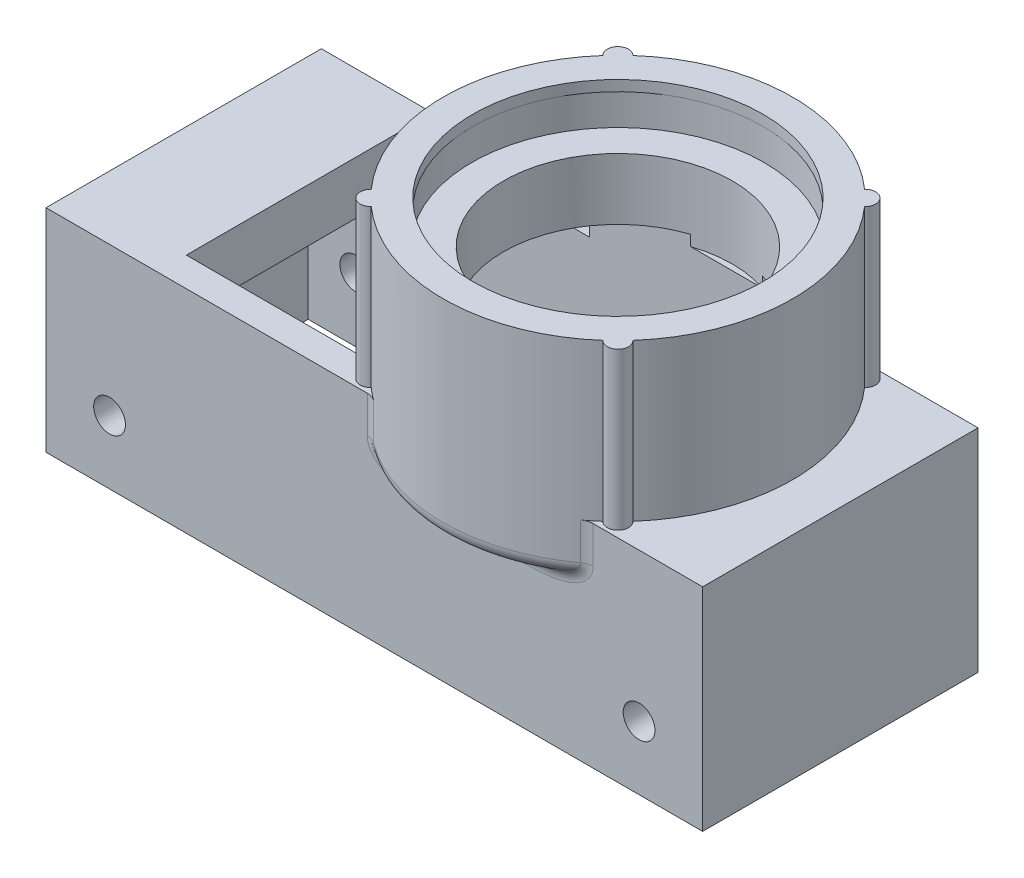
SolidWorks part; units mm, degrees
ref_plane "前视基准面" through (0, 0, 0) normal (0, 0, 1) x (1, 0, 0)
ref_plane "上视基准面" through (0, 0, 0) normal (0, 1, 0) x (1, 0, 0)
ref_plane "右视基准面" through (0, 0, 0) normal (1, 0, 0) x (0, 0, -1)
sketch "草图1" plane through (0, 0, 0) normal (0, 1, 0) x (1, 0, 0)
  line L1 (-20, -9.95) -> (20, -9.95)
  line L2 (-20, -9.95) -> (-20, 9.95)
  line L3 (-20, 9.95) -> (20, 9.95)
  line L4 (20, -9.95) -> (20, 9.95)
  line L5 (-20, -9.95) -> (20, 9.95) construction
  line L6 (-20, 9.95) -> (20, -9.95) construction
  line L7 (-28, -13) -> (28, -13)
  line L8 (-28, -13) -> (-28, 13)
  line L9 (-28, 13) -> (28, 13)
  line L10 (28, -13) -> (28, 13)
  line L11 (-28, -13) -> (28, 13) construction
  line L12 (-28, 13) -> (28, -13) construction
  point P0 (0, 0)
  point P6 (0, 0)
  dimension "D1" = 40
  dimension "D2" = 19.9
  dimension "D3" = 56
  dimension "D4" = 26
extrude "凸台-拉伸1" add sketch "草图1" along normal blind 5
sketch "草图2" plane through (0, 0, 0) normal (0, 1, 0) x (1, 0, 0)
  line L0 (0, 0) -> (0, 50000) construction
  line L1 (0, 0) -> (33.5112, 0) construction
  circle A0 centre (10, 0) radius 10
  circle A1 centre (10, 0) radius 13.5
  dimension "D2" = 20
  dimension "D3" = 27
  dimension "D1" = 10
extrude "凸台-拉伸2" add sketch "草图2" along normal blind 18.8
sketch "草图3" plane through (0, 0, 0) normal (0, 1, 0) x (1, 0, 0)
  circle A0 centre (10, 0) radius 16.5
  circle A1 centre (10, 0) radius 13.5 construction
  circle A2 centre (10, 0) radius 13.5
  dimension "D1" = 33
extrude "凸台-拉伸3" add sketch "草图3" along normal blind 22.8
sketch "草图4" plane through (0, 0, 0) normal (0, -1, 0) x (1, 0, 0)
  line L1 (-20, 9.95) -> (20, 9.95)
  line L2 (-20, 9.95) -> (-20, -9.95)
  line L3 (-20, -9.95) -> (20, -9.95)
  line L4 (20, 9.95) -> (20, -9.95)
  dimension "D1" = 19.9
  dimension "D2" = 40
extrude "切除-拉伸1" cut sketch "草图4" along direction (0, 1, 0) on the side against the normal blind 9
sketch "草图5" plane through (0, 0, 0) normal (0, -1, 0) x (1, 0, 0)
  line L0 (-20, 9.95) -> (-28, 9.95)
  line L1 (-28, 13) -> (28, 13)
  line L2 (-28, 13) -> (-28, 9.95)
  line L3 (-28, -13) -> (28, -13)
  line L4 (28, 13) -> (28, 9.95)
  line L5 (-20, 9.95) -> (20, 9.95)
  line L7 (-20, -9.95) -> (20, -9.95)
  line L9 (20, 9.95) -> (28, 9.95)
  line L10 (-20, -9.95) -> (-28, -9.95)
  line L11 (20, -9.95) -> (28, -9.95)
  line L12 (28, -9.95) -> (28, -13)
  line L13 (-28, -9.95) -> (-28, -13)
extrude "凸台-拉伸4" add sketch "草图5" along normal blind 15
sketch "草图6" plane through (28, 0, 0) normal (1, 0, 0) x (0, 0, -1)
  line L1 (-13, 5) -> (13, 5)
  line L2 (-13, 5) -> (-13, -15)
  line L3 (-13, -15) -> (13, -15)
  line L4 (13, 5) -> (13, -15)
extrude "凸台-拉伸5" add sketch "草图6" along normal blind 3
sketch "草图7" plane through (-28, 0, 0) normal (-1, 0, 0) x (0, 0, 1)
  line L1 (-13, 5) -> (13, 5)
  line L2 (-13, 5) -> (-13, -15)
  line L3 (-13, -15) -> (13, -15)
  line L4 (13, 5) -> (13, -15)
extrude "凸台-拉伸6" add sketch "草图7" along normal blind 3
sketch "草图11" plane through (0, 0, 0) normal (0, -1, 0) x (1, 0, 0)
  line L0 (-28, 0) -> (28, 0) construction
  circle A0 centre (-24.3, 4.5) radius 1
  circle A1 centre (-24.3, -4.5) radius 1
  dimension "D1" = 2
  dimension "D2" = 24.3
  dimension "D3" = 4.5
extrude "切除-拉伸5" cut sketch "草图11" against normal blind 4
mirror "镜向3" about plane through (0, 0, 0) normal (1, 0, 0) of "切除-拉伸5"
fillet "圆角3" radius 1.5 4 edges at (-0.1612, 2.5, -13) (20.1612, 2.5, -13) (10, 0, -13) (10, 0, -16.5)
fillet "圆角4" radius 1.5 4 edges at (-0.1612, 2.5, 13) (20.1612, 2.5, 13) (10, 0, 16.5) (10, 0, 13)
sketch "草图14" plane through (0, 0, 13) normal (0, 0, 1) x (1, 0, 0)
  line L0 (0, -15) -> (0, 24.7802) construction
  line L1 (31, -15) -> (-31, -15) construction
  line L2 (0, -9) -> (29.8623, -9) construction
  line L3 (-31, -15) -> (-31, 5) construction
  circle A0 centre (-25, -9) radius 1.5
  dimension "D2" = 3
  dimension "D1" = 6
  dimension "D3" = 6
extrude "切除-拉伸6" cut sketch "草图14" against normal through all
mirror "镜向4" about plane through (0, 0, 0) normal (1, 0, 0) of "切除-拉伸6"
sketch "草图15" plane through (0, 22.8, 0) normal (0, 1, 0) x (1, 0, 0)
  line L0 (10, 0) -> (36.2144, 0) construction
  line L1 (10, 0) -> (-5.1002, 15.1002) construction
  line L2 (10, 0) -> (21.6673, 11.6673) construction
  arc A4 (19.7766, -13.2917) -> (19.7766, 13.2917) centre (10, 0) ccw construction
  circle A5 centre (21.6673, 11.6673) radius 1
  circle A8 centre (-1.6673, -11.6673) radius 1
  circle A9 centre (10, 0) radius 16.5 construction
  circle A10 centre (21.6673, -11.6673) radius 1
  circle A11 centre (-1.6673, 11.6673) radius 1
  dimension "D3" = 2
  dimension "D4" = 2
  dimension "D5" = 2
  dimension "D6" = 2
  dimension "D1" = 45
  dimension "D2" = 45
extrude "凸台-拉伸7" add sketch "草图15" against normal up to surface (17.8 mm away) up to face at (-10.9404, 5, 0)
sketch "草图16" plane through (0, -15, 0) normal (0, -1, 0) x (1, 0, 0)
  line L0 (28, 9.95) -> (28, -9.95) construction
  line L1 (-29.5, -10.25) -> (29.5, -10.25)
  line L2 (-29.5, -10.25) -> (-29.5, 10.25)
  line L3 (-29.5, 10.25) -> (29.5, 10.25)
  line L4 (29.5, -10.25) -> (29.5, 10.25)
  line L5 (-29.5, -10.25) -> (29.5, 10.25) construction
  line L6 (-29.5, 10.25) -> (29.5, -10.25) construction
  point P0 (0, 0)
  dimension "D1" = 1.5
  dimension "D2" = 20.5
extrude "切除-拉伸7" cut sketch "草图16" against normal up to surface (15 mm away) up to face at (24.3, 0, 3.5)
sketch "草图17" plane through (0, 18.8, 0) normal (0, 1, 0) x (1, 0, 0)
  circle A0 centre (10, 0) radius 10.8
  dimension "D1" = 21.6
extrude "切除-拉伸8" cut sketch "草图17" against normal up to surface (9.8 mm away) up to face at (17.6384, 9, -7.2112)
sketch "草图18" plane through (0, 22.8, 0) normal (0, 1, 0) x (1, 0, 0)
  circle A0 centre (10, 0) radius 13.7
  dimension "D1" = 27.4
extrude "切除-拉伸9" cut sketch "草图18" against normal up to surface (4 mm away) up to face at (10, 18.8, 10.8)
fillet "圆角5" [suppressed] radius 1.5
sketch "草图19" plane through (0, 0, 0) normal (0, -1, 0) x (1, 0, 0)
  line L1 (-20.5, -10.25) -> (20.5, -10.25)
  line L2 (-20.5, -10.25) -> (-20.5, 10.25)
  line L3 (-20.5, 10.25) -> (20.5, 10.25)
  line L4 (20.5, -10.25) -> (20.5, 10.25)
  line L5 (-20.5, -10.25) -> (20.5, 10.25) construction
  line L6 (-20.5, 10.25) -> (20.5, -10.25) construction
  point P0 (0, 0)
  dimension "D1" = 20.5
  dimension "D2" = 41
extrude "切除-拉伸10" cut sketch "草图19" against normal blind 10
sketch "草图20" plane through (0, 18.8, 0) normal (0, 1, 0) x (1, 0, 0)
  circle A0 centre (10, 0) radius 13.8
  circle A1 centre (10, 0) radius 10.8
extrude "切除-拉伸11" cut sketch "草图20" against normal blind 3
sketch "草图21" plane through (0, 22.8, 0) normal (0, 1, 0) x (1, 0, 0)
  circle A0 centre (10, 0) radius 13.7 construction
  circle A1 centre (10, 0) radius 13.7
  arc A8 (-0.9391, -12.3526) -> (20.9391, -12.3526) centre (10, 0) ccw
  arc A9 (20.9391, -12.3526) -> (22.3526, -10.9391) centre (21.6673, -11.6673) ccw
  arc A10 (22.3526, -10.9391) -> (22.3526, 10.9391) centre (10, 0) ccw
  arc A11 (22.3526, 10.9391) -> (20.9391, 12.3526) centre (21.6673, 11.6673) ccw
  arc A12 (20.9391, 12.3526) -> (-0.9391, 12.3526) centre (10, 0) ccw
  arc A13 (-0.9391, 12.3526) -> (-2.3526, 10.9391) centre (-1.6673, 11.6673) ccw
  arc A14 (-2.3526, 10.9391) -> (-2.3526, -10.9391) centre (10, 0) ccw
  arc A15 (-2.3526, -10.9391) -> (-0.9391, -12.3526) centre (-1.6673, -11.6673) ccw
  arc A16 (-0.9391, -12.3526) -> (20.9391, -12.3526) centre (10, 0) ccw
  arc A17 (20.9391, -12.3526) -> (22.3526, -10.9391) centre (21.6673, -11.6673) ccw
  arc A18 (22.3526, -10.9391) -> (22.3526, 10.9391) centre (10, 0) ccw
  arc A19 (22.3526, 10.9391) -> (20.9391, 12.3526) centre (21.6673, 11.6673) ccw
  arc A20 (20.9391, 12.3526) -> (-0.9391, 12.3526) centre (10, 0) ccw
  arc A21 (-0.9391, 12.3526) -> (-2.3526, 10.9391) centre (-1.6673, 11.6673) ccw
  arc A22 (-2.3526, 10.9391) -> (-2.3526, -10.9391) centre (10, 0) ccw
  arc A23 (-2.3526, -10.9391) -> (-0.9391, -12.3526) centre (-1.6673, -11.6673) ccw
  dimension "D1" = 0
extrude "切除-拉伸12" cut sketch "草图21" against normal blind 3
